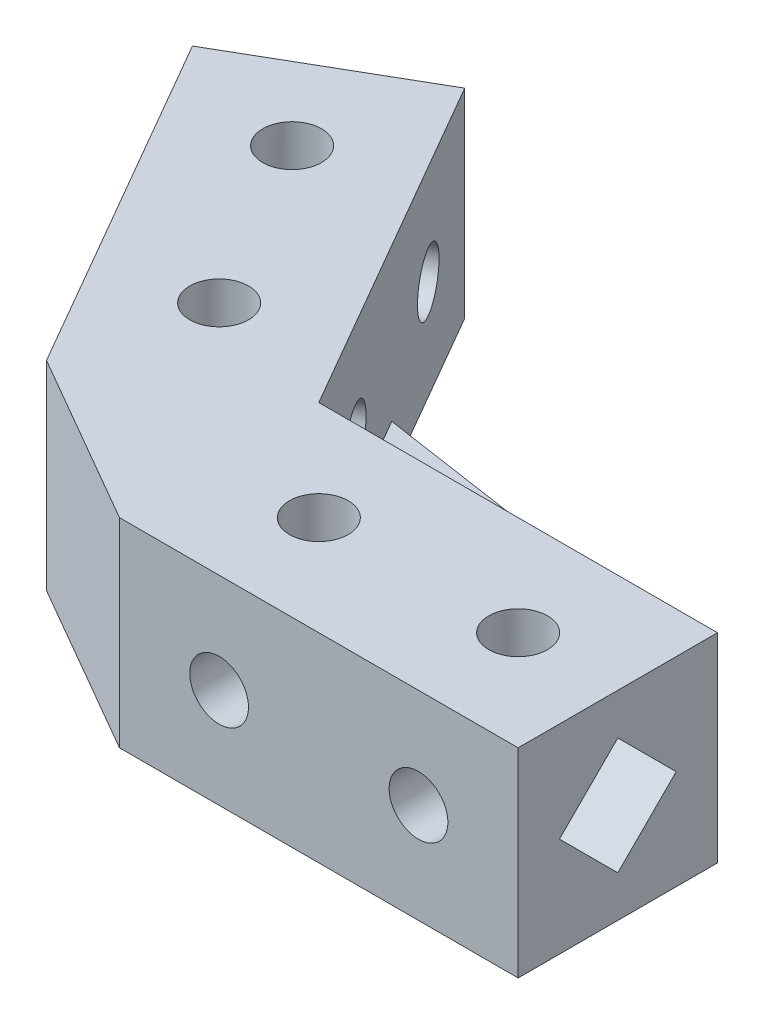
SolidWorks part; units mm, degrees
ref_plane "Front Plane" through (0, 0, 0) normal (0, 0, 1) x (1, 0, 0)
ref_plane "Top Plane" through (0, 0, 0) normal (0, 1, 0) x (1, 0, 0)
ref_plane "Right Plane" through (0, 0, 0) normal (1, 0, 0) x (0, 0, -1)
other "Configuration Table"
sketch "sketch1" plane through (0, 0, 0) normal (0, 1, 0) x (1, 0, 0)
  line L0 (0, -8.5) -> (8.5, -8.5) construction
  line L1 (0, 0) -> (34, 0)
  line L2 (0, 0) -> (0, -17)
  line L3 (0, -17) -> (34, -17)
  line L4 (34, 0) -> (34, -17)
  line L5 (8.5, -8.5) -> (25.5, -8.5) construction
  circle A1 centre (8.5, -8.5) radius 2.505
  circle A2 centre (25.5, -8.5) radius 2.505
  dimension "D4" = 5.01
  dimension "D1" = 17
  dimension "D2" = 34
  dimension "D3" = 8.5
  dimension "D6" = 17
extrude "Boss-Extrude1" add sketch "sketch1" along normal blind 17
sketch "Sketch6" plane through (0, 0, 0) normal (0, 0, -1) x (-1, 0, 0)
  line L0 (-34, 8.5) -> (-25.5, 8.5) construction
  line L1 (-25.5, 8.5) -> (-8.5, 8.5) construction
  line L4 (-34, 0) -> (0, 0)
  line L5 (0, 0) -> (0, 17)
  line L6 (0, 17) -> (-34, 17)
  line L7 (-34, 17) -> (-34, 0)
  line L8 (-34, 0) -> (0, 0)
  line L9 (0, 0) -> (0, 17)
  line L10 (0, 17) -> (-34, 17)
  line L11 (-34, 17) -> (-34, 0)
  circle A0 centre (-25.5, 8.5) radius 2.505
  circle A1 centre (-8.5, 8.5) radius 2.505
  dimension "D3" = 5.01
  dimension "D2" = 8.5
  dimension "D5" = 17
extrude "Cut-Extrude10" cut sketch "Sketch6" against normal through all flip side to cut
sketch "Sketch7" plane through (34, 0, 0) normal (1, 0, 0) x (0, 0, -1)
  line L0 (-17, 8.5) -> (0, 8.5) construction
  line L1 (-8.5, 8.5) -> (-8.5, 13.478) construction
  line L2 (-8.5, 13.478) -> (-3.522, 8.5)
  line L3 (-3.522, 8.5) -> (-8.5, 3.522)
  line L4 (-17, 0) -> (0, 0)
  line L5 (0, 0) -> (0, 17)
  line L6 (0, 17) -> (-17, 17)
  line L7 (-17, 17) -> (-17, 0)
  line L8 (-17, 0) -> (0, 0)
  line L9 (0, 0) -> (0, 17)
  line L10 (0, 17) -> (-17, 17)
  line L11 (-17, 17) -> (-17, 0)
  line L12 (-8.5, 3.522) -> (-13.478, 8.5)
  line L13 (-13.478, 8.5) -> (-8.5, 13.478)
  point P8 (0, 0)
  dimension "D2" = 7.04
extrude "Cut-Extrude11" cut sketch "Sketch7" against normal blind 34 flip side to cut
sketch "Sketch9" plane through (0, 0, 0) normal (0, 1, 0) x (1, 0, 0)
  line L0 (0, 0) -> (34, 0) construction
  line L1 (0, 0) -> (17, 29.4449) construction
  dimension "D1" = 60
ref_plane "Plane2" through (0, 0, 0) normal (-0.866, 0, -0.5) x (-0.5, 0, 0.866)
mirror "Mirror6" about plane through (0, 0, 0) normal (-0.866, 0, -0.5) of bodies 118 110
sketch "Sketch11" plane through (0, 0, 0) normal (0, 1, 0) x (1, 0, 0)
  line L0 (-14.7224, -8.5) -> (0, -17)
  line L1 (0, 0) -> (-14.7224, -8.5) construction
  line L2 (0, 0) -> (0, -17) construction
  line L3 (0, 0) -> (-14.7224, -8.5)
  line L4 (0, 0) -> (0, -17)
extrude "Boss-Extrude2" add sketch "Sketch11" along normal blind 17
sketch "Sketch13" plane through (0, 0, 0) normal (0, 1, 0) x (1, 0, 0)
  line L0 (-11.6112, 3.1112) -> (4.6528, 8.059) construction
  line L1 (0, 0) -> (17, 29.4449) construction
  line L2 (4.6528, 8.059) -> (8.5, -8.5) construction
  line L4 (7.1528, 12.3891) -> (-8.5, 14.7224)
  line L5 (-17, 29.4449) -> (0, 0) construction
  line L6 (7.1528, 12.3891) -> (17, 0)
  line L7 (0, 0) -> (34, 0) construction
  line L8 (0, 0) -> (17, 29.4449) construction
  line L9 (-8.5, 14.7224) -> (0, 0)
  line L10 (0, 0) -> (17, 0)
  circle A0 centre (8.5, -8.5) radius 2.505 construction
  circle A1 centre (-11.6112, 3.1112) radius 2.505 construction
  circle A2 centre (8.5, -8.5) radius 2.505 construction
  circle A3 centre (-11.6112, 3.1112) radius 2.505 construction
  circle A4 centre (4.6528, 8.059) radius 2.505
  dimension "D1" = 17
  dimension "D2" = 5.01
  dimension "D4" = 17
extrude "Boss-Extrude3" add sketch "Sketch13" along normal blind 4
equation "\"D2@sketch1\" = \"length\""
equation "\"holes\"= 2'Holes per side"
equation "\"cdist\"= 17mm'centre distance between holes"
equation "\"width\"= 17mm"
equation "\"length\"= \"cdist\" * \"holes\""
equation "\"D1@sketch1\"=\"width\""
equation "\"hdiam\"= 5.01mm'Hole diametre"
equation "\"D4@sketch1\" = \"hdiam\""
equation "\"D6@sketch1\" = \"cdist\""
equation "\"D5@sketch1\" = \"holes\""
equation "\"D2@Sketch6\"=\"cdist\"/2"
equation "\"D3@Sketch6\"=\"hdiam\""
equation "\"D5@Sketch6\"=\"cdist\""
equation "\"D4@Sketch6\"=\"holes\""
equation "\"D1@Boss-Extrude1\"=\"width\""
equation "\"joint\" = 120"
equation "\"D1@Sketch9\"=\"joint\"/2"
equation "\"D1@Boss-Extrude2\"=\"width\""
equation "\"D2@Sketch13\"=\"hdiam\""
equation "\"D4@Sketch13\"=\"cdist\""
equation "\"D1@Boss-Extrude3\"=\"supportheight\""
equation "\"supportheight\"= 4mm"
equation "\"tolerance\" = 0.04mm"
equation "\"insetwidth\"= 7mm"
equation "\"D2@Sketch7\"=\"insetwidth\"+\"tolerance\""
equation "\"D1@Cut-Extrude11\"=\"length\""
